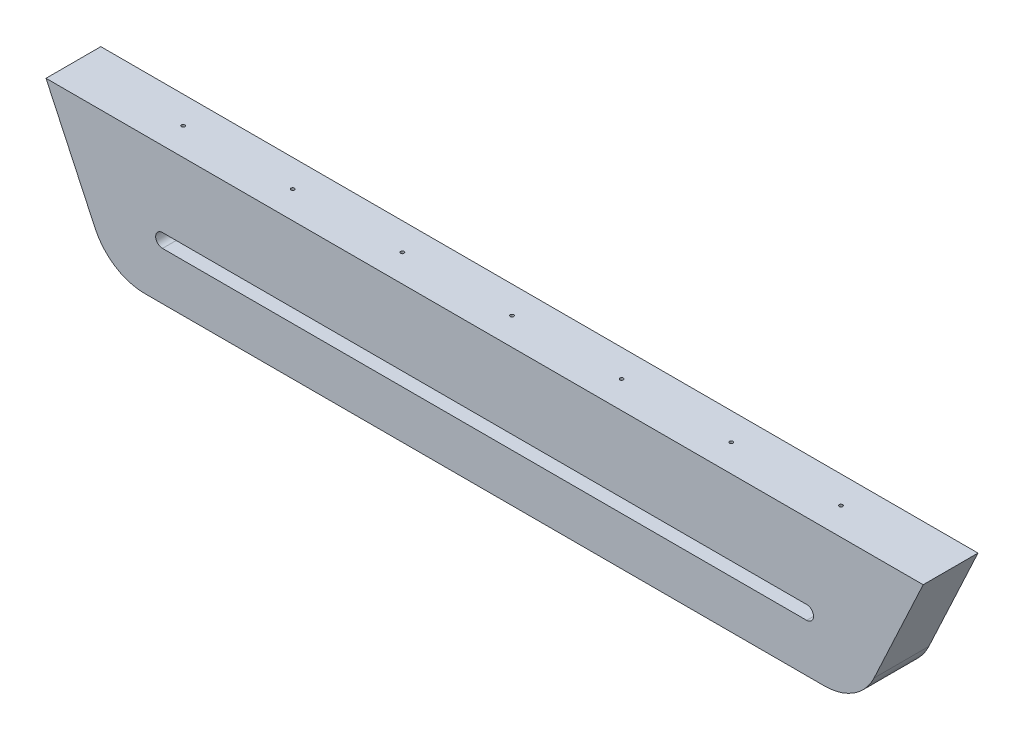
SolidWorks part; units mm, degrees
ref_plane "Front Plane" through (0, 0, 0) normal (0, 0, 1) x (1, 0, 0)
ref_plane "Top Plane" through (0, 0, 0) normal (0, 1, 0) x (1, 0, 0)
ref_plane "Right Plane" through (0, 0, 0) normal (1, 0, 0) x (0, 0, -1)
sketch "Sketch1" plane through (0, 0, 0) normal (0, 0, 1) x (1, 0, 0)
  line L0 (-203.2, 0) -> (203.2, 0)
  line L1 (203.2, 0) -> (173.5895, -63.5)
  line L2 (173.5895, -63.5) -> (-173.5895, -63.5)
  line L3 (-173.5895, -63.5) -> (-203.2, 0)
  line L4 (0, -63.5) -> (0, 0) construction
  dimension "D1" = 406.4
  dimension "D2" = 63.5
  dimension "D3" = 65
extrude "Boss-Extrude1" add sketch "Sketch1" along normal blind 25.4
fillet "Fillet1" radius 25.4 2 edges at (-173.5895, -63.5, 12.7) (173.5895, -63.5, 12.7)
hole_wizard "1/4 (0.25) Diameter Slot1" positions "Sketch2" profile "Sketch3" size "1/4" standard "ANSI Inch" slot yes end condition through all
sketch "Sketch2" plane through (0, 0, 25.4) normal (0, 0, 1) x (1, 0, 0)
  line L0 (-152.4, -38.1) -> (152.4, -38.1) construction
  line L1 (0, 0) -> (0, -38.1) construction
  line L2 (203.2, 0) -> (-203.2, 0) construction
  line L4 (0, -63.5) -> (0, -38.1) construction
  line L5 (-157.4079, -63.5) -> (157.4079, -63.5) construction
  point P0 (0, -38.1)
  dimension "D1" = 304.8
  dimension "D2" = 25.4
sketch "Sketch3" plane through (0, -38.1, 25.4) normal (1, 0, 0) x (0, -1, 0)
  line L0 (0, 0) -> (0, 25.4)
  line L1 (0, 25.4) -> (3.175, 25.4)
  line L2 (3.175, 25.4) -> (3.175, 0)
  line L5 (3.175, 0) -> (0, 0)
  line L11 (0, -6.35) -> (0, 107.95) construction
  dimension "Thru Hole Dia." = 6.35
  dimension "Thru Hole Depth" = 25.4
hole_wizard "1/16 (0.0625) Diameter Hole1" positions "Sketch4" profile "Sketch5" hole size "1/16" standard "ANSI Inch"
sketch "Sketch4" plane through (0, 0, 0) normal (0, 1, 0) x (1, 0, 0)
  line L0 (-203.2, -12.7) -> (-152.4, -12.7) construction
  line L1 (-203.2, -25.4) -> (-203.2, 0) construction
  point P0 (-152.4, -12.7)
  point P12 (-101.6, -12.7)
  point P13 (-50.8, -12.7)
  point P14 (0, -12.7)
  point P15 (50.8, -12.7)
  point P16 (101.6, -12.7)
  point P17 (152.4, -12.7)
  dimension "D2" = 50.8
  dimension "D3" = 50.8
  dimension "D1" = 7
sketch "Sketch5" plane through (-152.4, 0, 12.7) normal (1, 0, 0) x (0, 0, 1)
  line L0 (0, 0) -> (0, 13.1769)
  line L1 (0, 13.1769) -> (0.7937, 12.7)
  line L2 (0.7937, 12.7) -> (0.7937, 0)
  line L5 (0.7937, 0) -> (0, 0)
  line L10 (0, 13.1769) -> (-0.7937, 12.7) construction
  line L11 (0, -6.35) -> (0, 107.95) construction
  dimension "Hole Dia." = 1.5875
  dimension "Hole Depth" = 12.7
  dimension "Drill Angle" = 118
